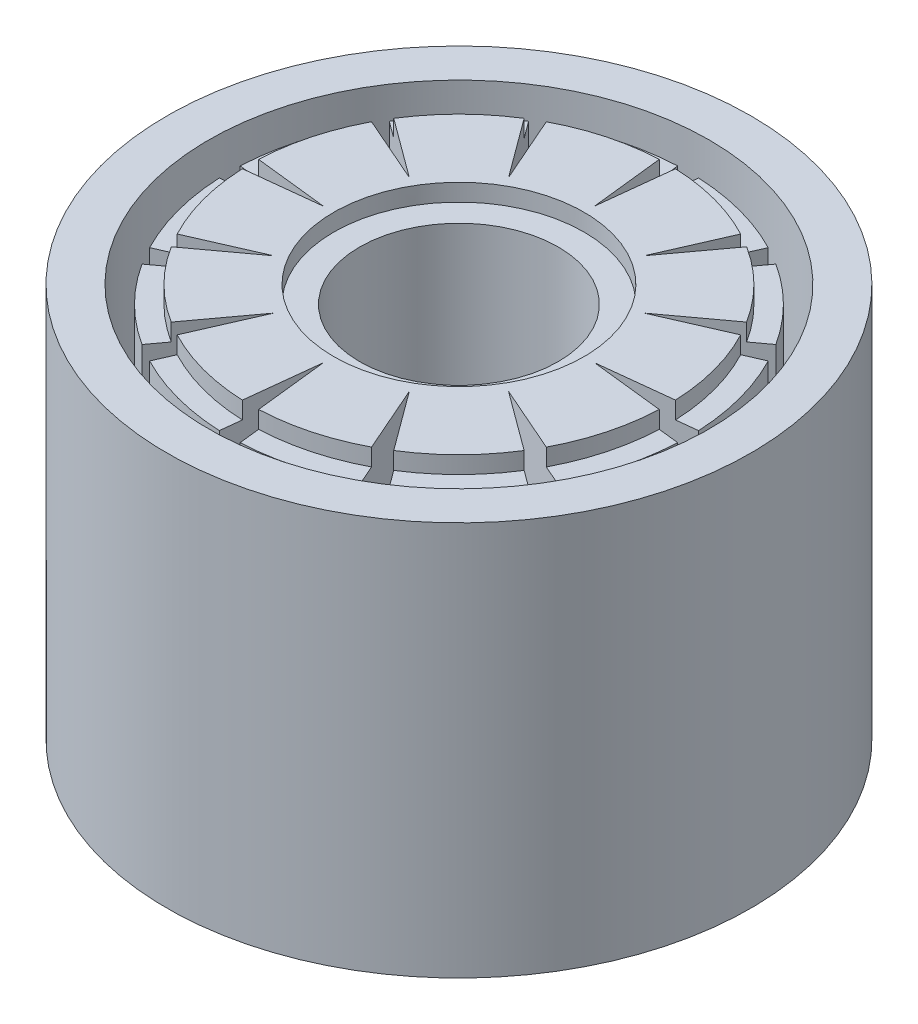
SolidWorks part; units mm, degrees
material "Cast Stainless Steel"
ref_plane "Front Plane" through (0, 0, 0) normal (0, 0, 1) x (1, 0, 0)
ref_plane "Top Plane" through (0, 0, 0) normal (0, 1, 0) x (1, 0, 0)
ref_plane "Right Plane" through (0, 0, 0) normal (1, 0, 0) x (0, 0, -1)
sketch "Sketch2" plane through (0, 0, 0) normal (0, 0, 1) x (1, 0, 0)
  line L0 (0, 0) -> (0, 21.3606) construction
  line L5 (4, 0) -> (12.5, 0)
  line L6 (12.5, 0) -> (14, 4)
  line L7 (14, 4) -> (14, 6)
  line L8 (14, 6) -> (6, 6)
  line L9 (6, 6) -> (6, 6.1)
  line L10 (6, 6.1) -> (11, 6.1)
  line L11 (11, 6.1) -> (11, 25)
  line L12 (11, 25) -> (4, 25)
  line L13 (4, 25) -> (4, 22)
  line L14 (4, 22) -> (3, 22)
  line L15 (3, 22) -> (3, 3)
  line L16 (3, 3) -> (4, 3)
  line L17 (4, 3) -> (4, 0)
  line L18 (14, 6) -> (14, 20.4229) construction
  line L19 (10, 25) -> (10, 24.175)
  line L20 (10, 24.175) -> (11, 24.175)
  line L21 (10, 6.1) -> (10, 6.925)
  line L22 (10, 6.925) -> (11, 6.925)
  dimension "D1" = 28
  dimension "D2" = 6
  dimension "D3" = 1.5
  dimension "D4" = 4
  dimension "D5" = 6
  dimension "D6" = 8
  dimension "D7" = 3
  dimension "D8" = 19
  dimension "D9" = 12
  dimension "D10" = 3
  dimension "D11" = 0.1
  dimension "D12" = 1
  dimension "D13" = 17.25
revolve "Revolve1" add sketch "Sketch2" angle 360 about L0 region at (7.4543, 11.8265, 0)
sketch "Sketch3" plane through (0, 0, 0) normal (0, 0, 1) x (1, 0, 0)
  line L0 (-11, 6.1) -> (11, 6.1) construction
  line L1 (14, 6.1) -> (12, 6.1)
  line L2 (14, 6.1) -> (14, 25)
  line L3 (14, 25) -> (12, 25)
  line L4 (12, 6.1) -> (12, 25)
  line L5 (11, 25) -> (-11, 25) construction
  line L6 (14, 4) -> (14, 6) construction
  line L7 (0, 0) -> (0, 26.8317) construction
  dimension "D1" = 2
revolve "Revolve2" add sketch "Sketch3" angle 360 about L7
sketch "Sketch4" plane through (0, 0, 0) normal (0, -1, 0) x (1, 0, 0)
  line L0 (0, 9.5) -> (0, -9.5) construction
  line L1 (-8, 0) -> (8, 0) construction
  circle A0 centre (-8, 0) radius 1.25
  circle A1 centre (0, 9.5) radius 1.25
  circle A2 centre (8, 0) radius 1.25
  circle A3 centre (0, -9.5) radius 1.25
  dimension "D3" = 2.5
  dimension "D1" = 16
  dimension "D2" = 19
extrude "Cut-Extrude1" cut sketch "Sketch4" against normal up to next (6 mm away)
sketch "Sketch5" plane through (0, 25, 0) normal (0, 1, 0) x (1, 0, 0)
  line L2 (0, 6.5) -> (-0.5, 10.9886)
  line L3 (0, 6.5) -> (0.5, 10.9886)
  circle A0 centre (0, 0) radius 6 construction
  circle A1 centre (0, 0) radius 6 construction
  circle A3 centre (0, 0) radius 11 construction
  arc A6 (-0.5, 10.9886) -> (0.5, 10.9886) centre (0, 0) cw
  circle A7 centre (0, 0) radius 6.5 construction
  circle A9 centre (0, 0) radius 11 construction
  point P13 (0, 11)
  dimension "D1" = 1
  dimension "D2" = 0.5
extrude "Cut-Extrude2" cut sketch "Sketch5" against normal up to surface (18.9 mm away) up to face at (0, 6.1, -10)
pattern_circular "CirPattern1" count 12 over 360 about axis through (0, 25, 0) along (0, -1, 0) of "Cut-Extrude2"
sketch "Sketch6" plane through (0, 25, 0) normal (0, 1, 0) x (1, 0, 0)
  circle A0 centre (0, 0) radius 6
  circle A1 centre (0, 0) radius 4.5
  dimension "D1" = 12
  dimension "D2" = 9
extrude "Cut-Extrude3" cut sketch "Sketch6" against normal up to surface (0.825 mm away) up to face at (2.685, 24.175, -10.0206)
sketch "Sketch7" plane through (0, 0, 0) normal (1, 0, 0) x (0, 0, -1)
  line L0 (0, 0) -> (0, 6.925)
  line L2 (-6, 6.1) -> (6, 6.1) construction
  line L3 (-6, 6.1) -> (6, 6.1) construction
  line L4 (0, 0) -> (14, 0)
  line L5 (14, 0) -> (14, 6.1)
  line L6 (14, 4) -> (14, 6) construction
  line L7 (0, 6.925) -> (6, 6.925)
  line L8 (6, 6.925) -> (6, 6.1)
  line L9 (6, 6.1) -> (14, 6.1)
  line L11 (6, 25) -> (-6, 25) construction
  line L12 (6, 24.175) -> (-6, 24.175) construction
  line L13 (6, 25) -> (-6, 25) construction
  line L14 (6, 24.175) -> (-6, 24.175) construction
  line L15 (0, 25) -> (0, 24.175) construction
revolve "Cut-Revolve1" cut sketch "Sketch7" angle 360 about L0
sketch "Sketch8" plane through (0, 6.925, 0) normal (0, -1, 0) x (1, 0, 0)
  circle A0 centre (0, 0) radius 4.7625
  dimension "D1" = 9.525
extrude "Cut-Extrude4" cut sketch "Sketch8" against normal through all
equation "\"D1@Sketch8\"=.375in"
